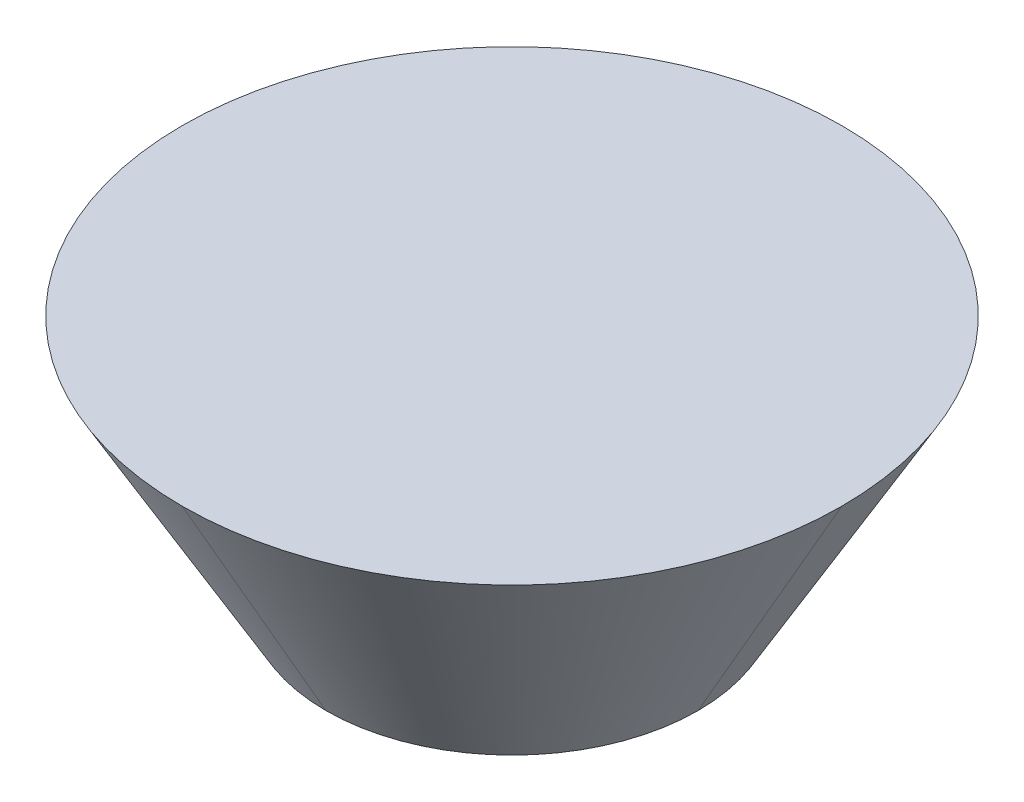
SolidWorks part; units mm, degrees
ref_plane "Front Plane" through (0, 0, 0) normal (0, 0, 1) x (1, 0, 0)
ref_plane "Top Plane" through (0, 0, 0) normal (0, 1, 0) x (1, 0, 0)
ref_plane "Right Plane" through (0, 0, 0) normal (1, 0, 0) x (0, 0, -1)
sketch "Sketch1" plane through (0, 0, 0) normal (0, 1, 0) x (1, 0, 0)
  line L1 (-25, -25) -> (25, -25)
  line L2 (-25, -25) -> (-25, 25)
  line L3 (-25, 25) -> (25, 25)
  line L4 (25, -25) -> (25, 25)
  line L5 (-25, -25) -> (25, 25) construction
  line L6 (-25, 25) -> (25, -25) construction
  point P0 (0, 0)
  dimension "D1" = 50
extrude "Boss-Extrude1" add sketch "Sketch1" along normal blind 18
fillet "Fillet1" radius 25 4 edges at (-25, 9, -25) (25, 9, -25) (25, 9, 25) (-25, 9, 25)
chamfer "Chamfer1" distance 20 angle 30 4 edges at (17.6777, 0, 17.6777) (17.6777, 0, -17.6777) (-17.6777, 0, -17.6777) (-17.6777, 0, 17.6777) first distance on face at (15.0888, 9, 15.0888) first distance on face at (15.0888, 9, -15.0888) first distance on face at (-15.0888, 9, -15.0888) first distance on face at (-15.0888, 9, 15.0888)
